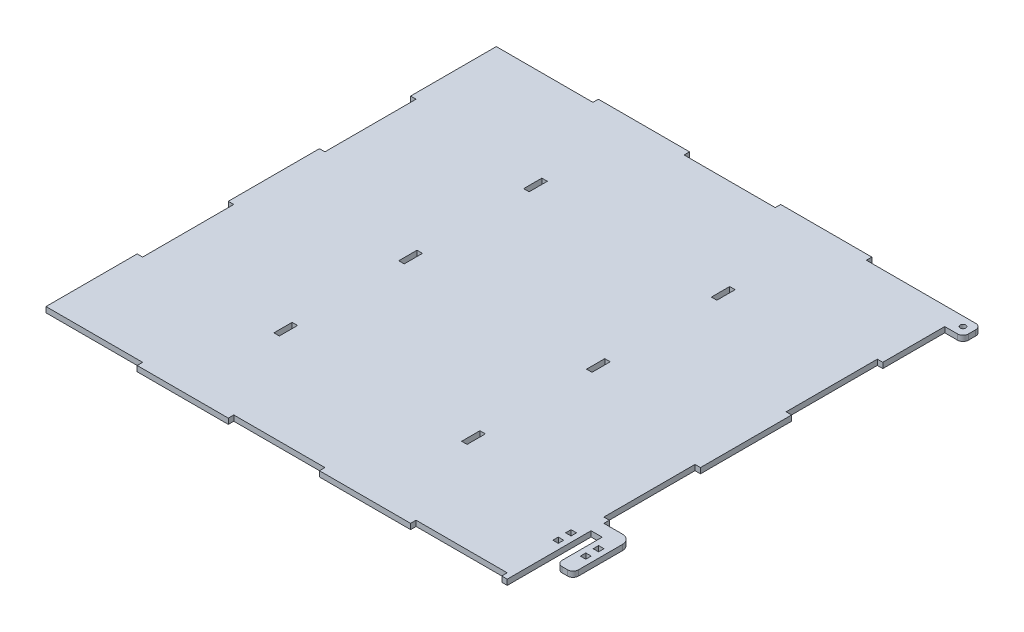
SolidWorks part; units mm, degrees
ref_plane "Front Plane" through (0, 0, 0) normal (0, 0, 1) x (1, 0, 0)
ref_plane "Top Plane" through (0, 0, 0) normal (0, 1, 0) x (1, 0, 0)
ref_plane "Right Plane" through (0, 0, 0) normal (1, 0, 0) x (0, 0, -1)
sketch "Sketch1" plane through (0, 0, 0) normal (0, 1, 0) x (1, 0, 0)
  line L0 (256, 103) -> (256, 153)
  line L1 (0, 0) -> (53, 0)
  line L2 (0, 0) -> (0, 50)
  line L3 (53, 250) -> (103, 250)
  line L4 (256, 0) -> (256, 43)
  line L5 (0, 200) -> (0, 247)
  line L6 (153, 250) -> (203, 250)
  line L7 (256, 50) -> (266.1, 50)
  line L8 (256, 0) -> (256, -3)
  line L9 (256, 203) -> (253, 203)
  line L10 (256, -3) -> (253, -3)
  line L11 (256, 153) -> (253, 153)
  line L12 (253, 203) -> (253, 153)
  line L13 (203, 0) -> (253, 0)
  line L14 (153, 0) -> (153, -3)
  line L15 (153, -3) -> (203, -3)
  line L16 (203, 0) -> (203, -3)
  line L17 (0, 200) -> (3, 200)
  line L18 (0, 100) -> (0, 150)
  line L19 (0, 150) -> (3, 150)
  line L20 (3, 200) -> (3, 150)
  line L21 (253, 0) -> (253, -3)
  line L22 (103, 0) -> (103, -3)
  line L23 (103, -3) -> (53, -3)
  line L24 (53, 0) -> (53, -3)
  line L25 (265.1, 28) -> (268.1, 28)
  line L26 (256, 43) -> (262.1, 43)
  line L27 (271.1, 45) -> (271.1, 43)
  line L28 (265.1, 28) -> (265.1, 31)
  line L29 (256, 103) -> (253, 103)
  line L30 (256, 203) -> (256, 237)
  line L32 (253, 103) -> (253, 53)
  line L33 (0, 100) -> (3, 100)
  line L34 (103, 0) -> (153, 0)
  line L35 (0, 50) -> (3, 50)
  line L36 (3, 100) -> (3, 50)
  line L37 (253, 247) -> (263, 247)
  line L38 (271.1, 43) -> (271.1, 21)
  line L39 (256, 237) -> (263, 237)
  line L40 (266, 244) -> (266, 240)
  line L41 (268.1, 18) -> (265.1, 18)
  line L42 (262.1, 43) -> (262.1, 21)
  line L43 (265.1, 31) -> (268.1, 31)
  line L44 (268.1, 28) -> (268.1, 31)
  line L45 (265.1, 35) -> (268.1, 35)
  line L46 (265.1, 35) -> (265.1, 38)
  line L47 (265.1, 38) -> (268.1, 38)
  line L48 (268.1, 35) -> (268.1, 38)
  line L49 (250, 28) -> (253, 28)
  line L50 (250, 28) -> (250, 31)
  line L51 (250, 31) -> (253, 31)
  line L52 (253, 28) -> (253, 31)
  line L53 (250, 35) -> (253, 35)
  line L54 (250, 35) -> (250, 38)
  line L55 (250, 38) -> (253, 38)
  line L56 (253, 35) -> (253, 38)
  line L57 (75, 50) -> (78, 50)
  line L58 (75, 50) -> (75, 60)
  line L59 (0, 247) -> (53, 247)
  line L60 (53, 250) -> (53, 247)
  line L61 (103, 247) -> (153, 247)
  line L62 (103, 247) -> (103, 250)
  line L63 (75, 60) -> (78, 60)
  line L64 (153, 247) -> (153, 250)
  line L65 (253, 53) -> (256, 53)
  line L66 (78, 50) -> (78, 60)
  line L67 (253, 247) -> (203, 247)
  line L68 (203, 250) -> (203, 247)
  line L69 (256, 50) -> (256, 53)
  line L70 (178, 50) -> (181, 50)
  line L71 (178, 50) -> (178, 60)
  line L72 (178, 60) -> (181, 60)
  line L73 (181, 50) -> (181, 60)
  line L74 (75, 118.5) -> (78, 118.5)
  line L75 (75, 118.5) -> (75, 128.5)
  line L76 (75, 128.5) -> (78, 128.5)
  line L77 (78, 118.5) -> (78, 128.5)
  line L78 (178, 118.5) -> (181, 118.5)
  line L79 (178, 118.5) -> (178, 128.5)
  line L80 (178, 128.5) -> (181, 128.5)
  line L81 (181, 118.5) -> (181, 128.5)
  line L82 (75, 187) -> (78, 187)
  line L83 (75, 187) -> (75, 197)
  line L84 (75, 197) -> (78, 197)
  line L85 (78, 187) -> (78, 197)
  line L86 (178, 187) -> (181, 187)
  line L87 (178, 187) -> (178, 197)
  line L88 (178, 197) -> (181, 197)
  line L89 (181, 187) -> (181, 197)
  circle A0 centre (261, 242) radius 1.5
  arc A1 (263, 247) -> (266, 244) centre (263, 244) cw
  arc A2 (263, 237) -> (266, 240) centre (263, 240) ccw
  arc A3 (266.1, 50) -> (271.1, 45) centre (266.1, 45) cw
  arc A4 (265.1, 18) -> (262.1, 21) centre (265.1, 21) cw
  arc A5 (271.1, 21) -> (268.1, 18) centre (268.1, 21) cw
  point P44 (266, 247)
  point P47 (266, 237)
  point P65 (251.5, 31)
  point P68 (271.1, 50)
  point P71 (262.1, 18)
  point P74 (271.1, 18)
  dimension "D7" = 3
  dimension "D8" = 5
  dimension "D9" = 5
  dimension "D10" = 3
  dimension "D45" = 5
  dimension "D46" = 3
  dimension "D1" = 256
  dimension "D3" = 50
  dimension "D4" = 3
  dimension "D5" = 10
  dimension "D6" = 10
  dimension "D11" = 47
  dimension "D12" = 34
  dimension "D13" = 10
  dimension "D14" = 10.1
  dimension "D15" = 3
  dimension "D16" = 3
  dimension "D17" = 50
  dimension "D18" = 53
  dimension "D19" = 50
  dimension "D20" = 50
  dimension "D21" = 50
  dimension "D22" = 50
  dimension "D23" = 50
  dimension "D24" = 5
  dimension "D25" = 44
  dimension "D26" = 3
  dimension "D27" = 3
  dimension "D28" = 3
  dimension "D29" = 50
  dimension "D30" = 7
  dimension "D31" = 25
  dimension "D32" = 9
  dimension "D33" = 6.1
  dimension "D34" = 43
  dimension "D35" = 25
  dimension "D36" = 4
  dimension "D37" = 4
  dimension "D38" = 10
  dimension "D39" = 3
  dimension "D40" = 10
  dimension "D41" = 3
  dimension "D42" = 3
  dimension "D43" = 3
  dimension "D44" = 3
  dimension "D47" = 53
  dimension "D48" = 50
  dimension "D49" = 50
  dimension "D50" = 50
  dimension "D51" = 247
  dimension "D52" = 3
  dimension "D53" = 50
  dimension "D54" = 3
  dimension "D55" = 3
  dimension "D56" = 50
  dimension "D57" = 10
  dimension "D58" = 58.5
  dimension "D59" = 58.5
  dimension "D60" = 58.5
  dimension "D61" = 58.5
  dimension "D62" = 50
  dimension "D63" = 50
  dimension "D64" = 100
  dimension "D65" = 75
extrude "Boss-Extrude1" add sketch "Sketch1" along normal blind 3
equation "\"w\"=3"
equation "\"L\"=50"
